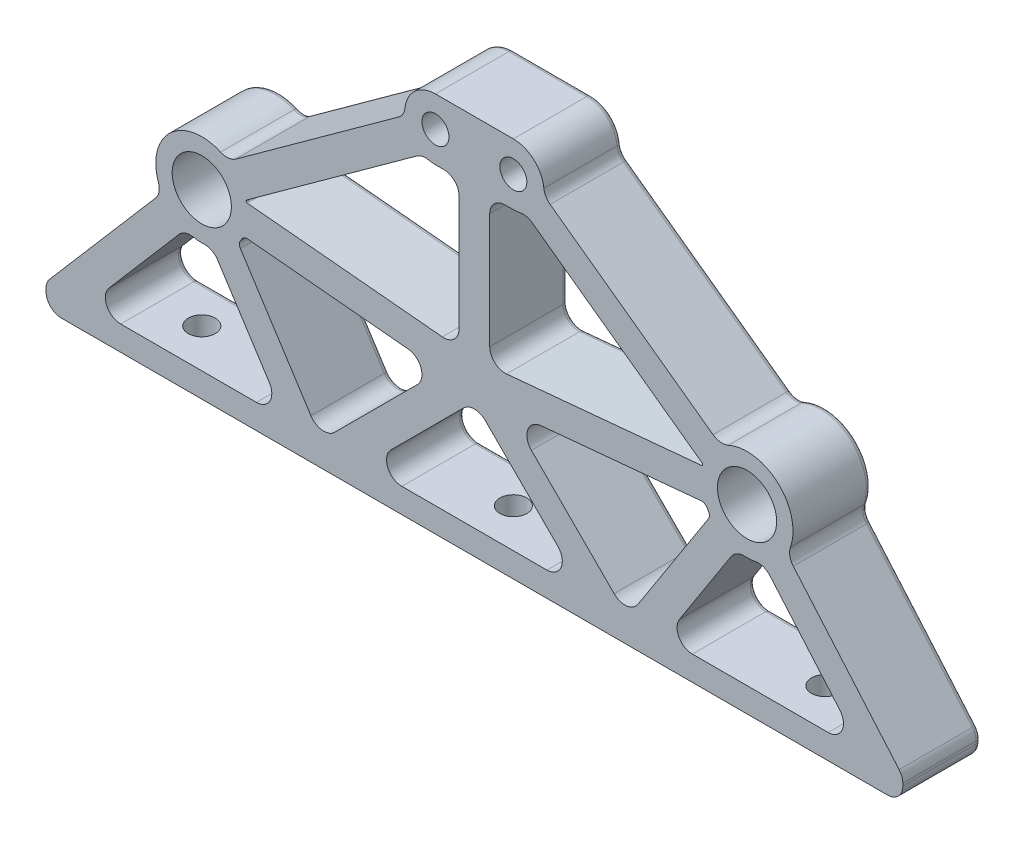
SolidWorks part; units mm, degrees
ref_plane "Front Plane" through (0, 0, 0) normal (0, 0, 1) x (1, 0, 0)
ref_plane "Top Plane" through (0, 0, 0) normal (0, 1, 0) x (1, 0, 0)
ref_plane "Right Plane" through (0, 0, 0) normal (1, 0, 0) x (0, 0, -1)
sketch "Sketch1" plane through (0, 0, 0) normal (0, 0, 1) x (1, 0, 0)
  line L0 (0, 0) -> (60.4965, 0) construction
  circle A0 centre (0, 0) radius 25.4 construction
  circle A1 centre (44.45, 35.921) radius 31.75 construction
  circle A2 centre (133.35, 35.921) radius 31.75 construction
  circle A3 centre (177.8, 0) radius 25.4 construction
  circle A4 centre (222.25, 35.921) radius 31.75 construction
  circle A5 centre (311.15, 35.921) radius 31.75 construction
  circle A6 centre (355.6, 0) radius 25.4 construction
  circle A7 centre (0, 0) radius 50.8 construction
  circle A8 centre (355.6, 0) radius 50.8 construction
  circle A9 centre (177.8, 0) radius 50.8 construction
  circle A10 centre (88.9, 35.921) radius 12.7 construction
  circle A11 centre (266.7, 35.921) radius 12.7 construction
  point P20 (-50.8, 0)
  point P21 (406.4, 0)
  dimension "D1" = 50.8
  dimension "D2" = 63.5
  dimension "D4" = 101.6
  dimension "D5" = 25.4
  dimension "D6" = 25.4
  dimension "D3" = 355.6
  dimension "D7" = 177.8
  dimension "D8" = 177.8
  dimension "D9" = 457.2
  dimension "D10" = 44.45
sketch "Sketch2" plane through (0, 0, 0) normal (0, 0, 1) x (1, 0, 0)
  line L0 (-200000, 0) -> (200060.4965, 0) construction
  line L1 (-44.45, 6.35) -> (400.05, 6.35) construction
  line L2 (-44.45, 6.35) -> (-44.45, -19.05) construction
  line L3 (-44.45, -19.05) -> (400.05, -19.05) construction
  line L4 (400.05, 6.35) -> (400.05, -19.05) construction
  circle A0 centre (-38.1, 0) radius 2.25 construction
  circle A2 centre (-31.75, -6.35) radius 2.25 construction
  circle A3 centre (-25.4, 0) radius 2.25 construction
  circle A4 centre (-12.7, 0) radius 2.25 construction
  circle A5 centre (0, 0) radius 2.25 construction
  circle A6 centre (12.7, 0) radius 2.25 construction
  circle A7 centre (25.4, 0) radius 2.25 construction
  circle A8 centre (38.1, 0) radius 2.25 construction
  circle A9 centre (50.8, 0) radius 2.25 construction
  circle A10 centre (63.5, 0) radius 2.25 construction
  circle A11 centre (76.2, 0) radius 2.25 construction
  circle A12 centre (88.9, 0) radius 2.25 construction
  circle A13 centre (101.6, 0) radius 2.25 construction
  circle A14 centre (114.3, 0) radius 2.25 construction
  circle A15 centre (127, 0) radius 2.25 construction
  circle A16 centre (139.7, 0) radius 2.25 construction
  circle A17 centre (152.4, 0) radius 2.25 construction
  circle A18 centre (165.1, 0) radius 2.25 construction
  circle A19 centre (177.8, 0) radius 2.25 construction
  circle A20 centre (190.5, 0) radius 2.25 construction
  circle A21 centre (203.2, 0) radius 2.25 construction
  circle A22 centre (215.9, 0) radius 2.25 construction
  circle A23 centre (228.6, 0) radius 2.25 construction
  circle A24 centre (241.3, 0) radius 2.25 construction
  circle A25 centre (254, 0) radius 2.25 construction
  circle A26 centre (266.7, 0) radius 2.25 construction
  circle A27 centre (279.4, 0) radius 2.25 construction
  circle A28 centre (292.1, 0) radius 2.25 construction
  circle A29 centre (304.8, 0) radius 2.25 construction
  circle A30 centre (317.5, 0) radius 2.25 construction
  circle A31 centre (330.2, 0) radius 2.25 construction
  circle A32 centre (342.9, 0) radius 2.25 construction
  circle A33 centre (355.6, 0) radius 2.25 construction
  circle A34 centre (368.3, 0) radius 2.25 construction
  circle A35 centre (381, 0) radius 2.25 construction
  circle A36 centre (393.7, 0) radius 2.25 construction
  circle A37 centre (-25.4, -12.7) radius 2.25 construction
  circle A38 centre (-12.7, -12.7) radius 2.25 construction
  circle A39 centre (0, -12.7) radius 2.25 construction
  circle A40 centre (12.7, -12.7) radius 2.25 construction
  circle A41 centre (25.4, -12.7) radius 2.25 construction
  circle A42 centre (38.1, -12.7) radius 2.25 construction
  circle A43 centre (50.8, -12.7) radius 2.25 construction
  circle A44 centre (63.5, -12.7) radius 2.25 construction
  circle A45 centre (76.2, -12.7) radius 2.25 construction
  circle A46 centre (88.9, -12.7) radius 2.25 construction
  circle A47 centre (101.6, -12.7) radius 2.25 construction
  circle A48 centre (114.3, -12.7) radius 2.25 construction
  circle A49 centre (127, -12.7) radius 2.25 construction
  circle A50 centre (139.7, -12.7) radius 2.25 construction
  circle A51 centre (152.4, -12.7) radius 2.25 construction
  circle A52 centre (165.1, -12.7) radius 2.25 construction
  circle A53 centre (177.8, -12.7) radius 2.25 construction
  circle A54 centre (190.5, -12.7) radius 2.25 construction
  circle A55 centre (203.2, -12.7) radius 2.25 construction
  circle A56 centre (215.9, -12.7) radius 2.25 construction
  circle A57 centre (228.6, -12.7) radius 2.25 construction
  circle A58 centre (241.3, -12.7) radius 2.25 construction
  circle A59 centre (254, -12.7) radius 2.25 construction
  circle A60 centre (266.7, -12.7) radius 2.25 construction
  circle A61 centre (279.4, -12.7) radius 2.25 construction
  circle A62 centre (292.1, -12.7) radius 2.25 construction
  circle A63 centre (304.8, -12.7) radius 2.25 construction
  circle A64 centre (317.5, -12.7) radius 2.25 construction
  circle A65 centre (330.2, -12.7) radius 2.25 construction
  circle A66 centre (342.9, -12.7) radius 2.25 construction
  circle A67 centre (355.6, -12.7) radius 2.25 construction
  circle A68 centre (368.3, -12.7) radius 2.25 construction
  circle A69 centre (381, -12.7) radius 2.25 construction
  circle A70 centre (393.7, -12.7) radius 2.25 construction
  circle A71 centre (-38.1, -12.7) radius 2.25 construction
  circle A72 centre (-19.05, -6.35) radius 2.25 construction
  circle A73 centre (-6.35, -6.35) radius 2.25 construction
  circle A74 centre (6.35, -6.35) radius 2.25 construction
  circle A75 centre (19.05, -6.35) radius 2.25 construction
  circle A76 centre (31.75, -6.35) radius 2.25 construction
  circle A77 centre (44.45, -6.35) radius 2.25 construction
  circle A78 centre (57.15, -6.35) radius 2.25 construction
  circle A79 centre (69.85, -6.35) radius 2.25 construction
  circle A80 centre (82.55, -6.35) radius 2.25 construction
  circle A81 centre (95.25, -6.35) radius 2.25 construction
  circle A82 centre (107.95, -6.35) radius 2.25 construction
  circle A83 centre (120.65, -6.35) radius 2.25 construction
  circle A84 centre (133.35, -6.35) radius 2.25 construction
  circle A85 centre (146.05, -6.35) radius 2.25 construction
  circle A86 centre (158.75, -6.35) radius 2.25 construction
  circle A87 centre (171.45, -6.35) radius 2.25 construction
  circle A88 centre (184.15, -6.35) radius 2.25 construction
  circle A89 centre (196.85, -6.35) radius 2.25 construction
  circle A90 centre (209.55, -6.35) radius 2.25 construction
  circle A91 centre (222.25, -6.35) radius 2.25 construction
  circle A92 centre (234.95, -6.35) radius 2.25 construction
  circle A93 centre (247.65, -6.35) radius 2.25 construction
  circle A94 centre (260.35, -6.35) radius 2.25 construction
  circle A95 centre (273.05, -6.35) radius 2.25 construction
  circle A96 centre (285.75, -6.35) radius 2.25 construction
  circle A97 centre (298.45, -6.35) radius 2.25 construction
  circle A98 centre (311.15, -6.35) radius 2.25 construction
  circle A99 centre (323.85, -6.35) radius 2.25 construction
  circle A100 centre (336.55, -6.35) radius 2.25 construction
  circle A101 centre (349.25, -6.35) radius 2.25 construction
  circle A102 centre (361.95, -6.35) radius 2.25 construction
  circle A103 centre (374.65, -6.35) radius 2.25 construction
  circle A104 centre (387.35, -6.35) radius 2.25 construction
  dimension "D5" = 4.5
  dimension "D1" = 25.4
  dimension "D2" = 444.5
  dimension "D3" = 6.35
  dimension "D4" = 44.45
  dimension "D6" = 6.35
  dimension "D7" = 6.35
  dimension "D8" = 6.35
  dimension "D12" = 12.7
  dimension "D9" = 35
  dimension "D10" = 2
  dimension "D11" = 34
sketch "Sketch3" plane through (0, 0, 0) normal (0, 0, 1) x (1, 0, 0)
  line L0 (44.45, 35.921) -> (88.9, 31.75) construction
  line L1 (88.9, 31.75) -> (133.35, 35.921) construction
  line L2 (44.45, 35.921) -> (19.05, 6.35) construction
  line L3 (-44.45, 6.35) -> (400.05, 6.35) construction
  line L4 (19.05, 6.35) -> (158.75, 6.35) construction
  line L5 (158.75, 6.35) -> (133.35, 35.921) construction
  line L6 (44.45, 35.921) -> (63.5, 6.35) construction
  line L7 (63.5, 6.35) -> (88.9, 31.75) construction
  line L8 (88.9, 31.75) -> (114.3, 6.35) construction
  line L9 (114.3, 6.35) -> (133.35, 35.921) construction
  line L10 (19.05, 6.35) -> (158.75, 6.35)
  line L11 (158.75, 6.35) -> (158.75, 10.1868)
  line L12 (158.75, 10.1868) -> (139.8538, 32.186)
  line L13 (88.9, 34.261) -> (126.0763, 37.7495)
  line L14 (126.5434, 32.7713) -> (94.4278, 29.7577)
  line L15 (152.0186, 10.35) -> (119.8507, 10.35)
  line L16 (119.8507, 10.35) -> (131.6222, 28.6228)
  line L17 (152.0186, 10.35) -> (136.0609, 28.9281)
  line L18 (113.8766, 10.309) -> (127.4189, 31.3306)
  line L19 (113.8766, 10.309) -> (94.4278, 29.7577)
  line L20 (106.7645, 10.35) -> (71.0355, 10.35)
  line L21 (71.0355, 10.35) -> (88.9, 28.2145)
  line L22 (106.7645, 10.35) -> (88.9, 28.2145)
  line L24 (51.2566, 32.7713) -> (83.3722, 29.7577)
  line L26 (25.7814, 10.35) -> (57.9493, 10.35)
  line L27 (57.9493, 10.35) -> (46.1778, 28.6228)
  line L28 (25.7814, 10.35) -> (41.7391, 28.9281)
  line L29 (19.05, 6.35) -> (19.05, 10.1868)
  line L30 (19.05, 10.1868) -> (37.9462, 32.186)
  line L31 (51.7237, 37.7495) -> (88.9, 34.261)
  line L32 (63.9234, 10.309) -> (50.3811, 31.3306)
  line L33 (63.9234, 10.309) -> (83.3722, 29.7577)
  circle A0 centre (44.45, 35.921) radius 4.826
  circle A2 centre (133.35, 35.921) radius 4.826
  circle A3 centre (44.45, 35.921) radius 7.5
  circle A5 centre (133.35, 35.921) radius 7.5
  circle A6 centre (44.45, 35.921) radius 2.5
  circle A7 centre (133.35, 35.921) radius 2.5
  dimension "D1" = 9.652
  dimension "D2" = 15
  dimension "D3" = 5
  dimension "D20" = 5
  dimension "Thickness" = 5
  dimension "D4" = 2.5
  dimension "D5" = 2.5
  dimension "D6" = 5
  dimension "D7" = 2.5
  dimension "D8" = 5
  dimension "D9" = 2.5
  dimension "D10" = 5
  dimension "D11" = 5
  dimension "D12" = 2.5
  dimension "D13" = 4
  dimension "D14" = 2.5
  dimension "D15" = 5
  dimension "D16" = 5
  dimension "D17" = 5
  dimension "D18" = 2.5
  dimension "D19" = 25.4
extrude "Boss-Extrude1" add sketch "Sketch3" along normal blind 12.7 contours A5 L13 L31 A3 L24 L33 L32 L27 L26 L28 L30 L29 L10 L11 L12 L17 L15 L16 L18 L19 L14 L22 L20 L21 | A3 A0 | A5 A2 region at (20.4819, 8.2684, 0) region at (41.7212, 42.6787, 0) region at (138.0986, 30.3926, 0)
sketch "Sketch5" plane through (0, 0, 0) normal (0, 0, -1) x (-1, 0, 0)
  line L0 (-88.9, 34.261) -> (-88.9, 11.7037) construction
  line L1 (-95.25, 63.5) -> (-82.55, 63.5) construction
  line L2 (-95.25, 68.5) -> (-82.55, 68.5)
  line L3 (-95.25, 58.5) -> (-82.55, 58.5)
  line L4 (-19.05, 6.35) -> (-158.75, 6.35) construction
  line L5 (-51.7237, 37.7495) -> (-88.9, 34.261) construction
  line L6 (-88.9, 34.261) -> (-126.0763, 37.7495) construction
  line L7 (-51.7237, 37.7495) -> (-88.9, 34.261)
  line L8 (-88.9, 34.261) -> (-126.0763, 37.7495)
  line L9 (-91.4, 34.4956) -> (-91.4, 58.5)
  line L10 (-86.4, 34.4956) -> (-86.4, 58.5)
  line L11 (-126.1562, 38.0421) -> (-97.2917, 58.9359)
  line L12 (-129.088, 42.0923) -> (-100.2235, 62.9861)
  line L13 (-80.5083, 58.9359) -> (-51.6438, 38.0421)
  line L14 (-48.712, 42.0923) -> (-77.5765, 62.9861)
  line L15 (-133.35, 35.921) -> (-95.25, 63.5) construction
  line L16 (-82.55, 63.5) -> (-44.45, 35.921) construction
  arc A2 (-37.9462, 32.186) -> (-51.7237, 37.7495) centre (-44.45, 35.921) ccw construction
  arc A3 (-126.0763, 37.7495) -> (-139.8538, 32.186) centre (-133.35, 35.921) ccw construction
  arc A4 (-37.9462, 32.186) -> (-51.7237, 37.7495) centre (-44.45, 35.921) ccw
  arc A5 (-126.0763, 37.7495) -> (-139.8538, 32.186) centre (-133.35, 35.921) ccw
  arc A6 (-95.25, 68.5) -> (-95.25, 58.5) centre (-95.25, 63.5) ccw
  arc A7 (-82.55, 58.5) -> (-82.55, 68.5) centre (-82.55, 63.5) ccw
  circle A8 centre (-95.25, 63.5) radius 2.2
  circle A9 centre (-82.55, 63.5) radius 2.2
  point P0 (-88.9, 34.261)
  point P3 (-133.35, 35.921)
  point P4 (-44.45, 35.921)
  point P5 (-88.9, 63.5)
  point P10 (-88.9, 6.35)
  line M16 (-51.7237, 37.7495) -> (-88.9, 34.261)
  line M17 (-88.9, 34.261) -> (-126.0763, 37.7495)
  arc M18 (-126.0763, 37.7495) -> (-139.8538, 32.186) centre (-133.35, 35.921) ccw
  arc M24 (-37.9462, 32.186) -> (-51.7237, 37.7495) centre (-44.45, 35.921) ccw
  dimension "D5" = 10
  dimension "D6" = 57.15
  dimension "D7" = 4.4
  dimension "D1" = 12.7
  dimension "D2" = 5
  dimension "D3" = 5
  dimension "D4" = 5
extrude "Boss-Extrude3" add sketch "Sketch5" against normal blind 12.7 contours L9 L7 L10 M17 | L12 L11 M18 M17 | L13 L14 M16 M24 | L3 A7 L2 A6 A9 A8 region at (88.9, 63.5, 0) region at (113.2565, 50.4658, 0) region at (64.5435, 50.4658, 0) region at (88.9, 46.439, 0)
fillet "Fillet1" radius 2.5 31 edges at (158.75, 6.35, 6.35) (158.75, 10.1868, 6.35) (19.05, 6.35, 6.35) (19.05, 10.1868, 6.35) (139.8538, 32.186, 6.35) (152.0186, 10.35, 6.35) (136.0609, 28.9281, 6.35) (131.6222, 28.6228, 6.35) (119.8507, 10.35, 6.35) (113.8766, 10.309, 6.35) (106.7645, 10.35, 6.35) (25.7814, 10.35, 6.35) (41.7391, 28.9281, 6.35) (46.1778, 28.6228, 6.35) (57.9493, 10.35, 6.35) (71.0355, 10.35, 6.35) (63.9234, 10.309, 6.35) (37.9462, 32.186, 6.35) (88.9, 28.2145, 6.35) (94.4278, 29.7577, 6.35) (83.3722, 29.7577, 6.35) (91.4, 34.4956, 6.35) (86.4, 34.4956, 6.35) (129.088, 42.0923, 6.35) (48.712, 42.0923, 6.35) (100.2235, 62.9861, 6.35) (77.5765, 62.9861, 6.35) (80.5083, 58.9359, 6.35) (86.4, 58.5, 6.35) (91.4, 58.5, 6.35) (97.2917, 58.9359, 6.35)
fillet "Fillet5" radius 0.2 4 edges at (126.0763, 37.7495, 6.35) (126.1562, 38.0421, 6.35) (51.7237, 37.7495, 6.35) (51.6438, 38.0421, 6.35)
fillet "Fillet6" radius 1 4 edges at (50.3811, 31.3306, 6.35) (51.2566, 32.7713, 6.35) (126.5434, 32.7713, 6.35) (127.4189, 31.3306, 6.35)
sketch "Sketch4" plane through (0, 6.35, 0) normal (0, -1, 0) x (1, 0, 0)
  line L0 (21.55, 12.7) -> (21.55, 0) construction
  circle A0 centre (38.1, 6.35) radius 2.2
  circle A1 centre (88.9, 6.35) radius 2.2
  circle A2 centre (139.7, 6.35) radius 2.2
  point P0 (139.7, 0)
  point P2 (88.9, 0)
  point P4 (38.1, 0)
  point P15 (21.55, 6.35)
  dimension "D1" = 4.4
extrude "Cut-Extrude1" cut sketch "Sketch4" against normal up to next
extrude "Boss-Extrude2" add sketch "Sketch3<3>" along normal blind 3.175 contours A0 | A2 region at (39.7605, 35.921, 0) region at (128.6605, 35.921, 0)
sketch "Sketch3<3>" plane through (0, 0, 0) normal (0, 0, 1) x (1, 0, 0) same geometry as "Sketch3"
fillet "Fillet2" radius 0.75 86 edges at (135.85, 35.921, 0) (46.95, 35.921, 0) (74.7614, 11.8933, 0) (81.2178, 20.5322, 0) (88.9, 27.1789, 0) (96.5822, 20.5322, 0) (103.0386, 11.8933, 0) (88.9, 10.35, 0) (136.0279, 28.4526, 0) (142.7842, 21.1008, 0) (148.8474, 11.8065, 0) (135.5053, 10.35, 0) (122.2402, 11.6531, 0) (126.5475, 20.7453, 0) (131.7201, 28.1562, 0) (133.8647, 28.4387, 0) (46.0799, 28.1562, 0) (51.2525, 20.7453, 0) (55.5598, 11.6531, 0) (42.2947, 10.35, 0) (28.9526, 11.8065, 0) (35.0158, 21.1008, 0) (41.7721, 28.4526, 0) (43.9353, 28.4387, 0) (65.0032, 31.4814, 0) (80.1963, 28.6131, 0) (72.8634, 19.2489, 0) (64.081, 11.7821, 0) (56.4959, 21.8386, 0) (158.5943, 10.1291, 0) (149.5179, 20.935, 0) (140.3289, 32.1469, 0) (138.4284, 41.4401, 0) (110.0352, 36.2442, 0) (67.7648, 36.2442, 0) (39.3716, 41.4401, 0) (37.4711, 32.1469, 0) (28.2821, 20.935, 0) (19.2057, 10.1291, 0) (19.05, 9.0553, 0) (19.7822, 7.0822, 0) (88.9, 6.35, 0) (158.0178, 7.0822, 0) (158.75, 9.0553, 0) (121.3041, 21.8386, 0) (113.719, 11.7821, 0) (104.9366, 19.2489, 0) (97.6037, 28.6131, 0) (112.7968, 31.4814, 0) (86.4, 46.6206, 0) (65.6224, 48.1606, 0) (114.5224, 52.6357, 0) (63.2776, 52.6357, 0) (112.1776, 48.1606, 0) (91.4, 46.6206, 0) (85.5832, 35.3926, 0) (129.0096, 42.5625, 0) (48.7904, 42.5625, 0) (92.2168, 35.3926, 0) (93.05, 63.5, 0) (80.35, 63.5, 0) (83.225, 58.5, 0) (88.9, 68.5, 0) (79.2015, 67.2131, 0) (95.7852, 58.5287, 0) (80.4421, 58.619, 0) (82.0148, 58.5287, 0) (85.6678, 57.7678, 0) (100.5452, 63.0222, 0) (98.5985, 67.2131, 0) (77.2548, 63.0222, 0) (92.1322, 57.7678, 0) (94.575, 58.5, 0) (97.3579, 58.619, 0) (50.5872, 31.3057, 0) (50.8594, 32.0263, 0) (51.3736, 32.5998, 0) (51.6858, 38.0285, 0) (51.753, 37.7825, 0) (51.6852, 37.8962, 0) (127.2128, 31.3057, 0) (126.4264, 32.5998, 0) (126.9406, 32.0263, 0) (126.1142, 38.0285, 0) (126.1148, 37.8962, 0) (126.047, 37.7825, 0)
